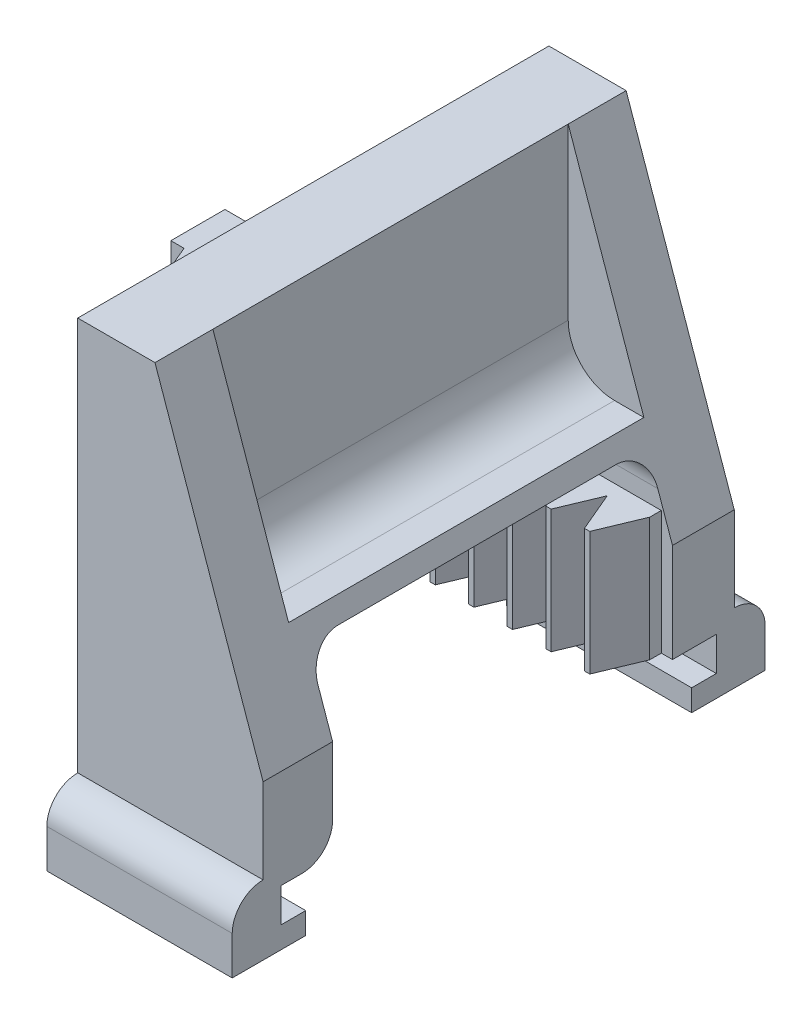
SolidWorks part; units mm, degrees
ref_plane "Front Plane" through (0, 0, 0) normal (0, 0, 1) x (1, 0, 0)
ref_plane "Top Plane" through (0, 0, 0) normal (0, 1, 0) x (1, 0, 0)
ref_plane "Right Plane" through (0, 0, 0) normal (1, 0, 0) x (0, 0, -1)
sketch "Sketch1" plane through (0, 0, 0) normal (0, 0, 1) x (1, 0, 0)
  line L0 (0, 0) -> (0, -30)
  line L1 (0, -30) -> (12, -30)
  line L2 (12, -30) -> (12, -20)
  line L3 (12, -20) -> (5, 0)
  line L4 (5, 0) -> (0, 0)
  dimension "D1" = 30
  dimension "D2" = 12
  dimension "D3" = 10
  dimension "D4" = 5
extrude "Boss-Extrude1" add sketch "Sketch1" against normal blind 30.5
sketch "Sketch4" plane through (0, 0, 0) normal (-1, 0, 0) x (0, 0, 1)
  line L0 (-30.5, 0) -> (-30.5, -30) construction
  line L1 (-26.5, -15.288) -> (-4.5, -15.288)
  line L2 (-26.5, -15.288) -> (-26.5, -30.288)
  line L3 (-26.5, -30.288) -> (-4.5, -30.288)
  line L4 (-4.5, -15.288) -> (-4.5, -30.288)
  point P4 (-26.5, -22.788)
  dimension "D1" = 22
  dimension "D2" = 15
  dimension "D3" = 4
extrude "Cut-Extrude2" cut sketch "Sketch4" against normal blind 25 contours L2 L1 L4 L3
ref_plane "Plane1" through (0, 0, -15.25) normal (0, 0, 1) x (1, 0, 0)
sketch "Sketch6" plane through (0, 0, -15.25) normal (0, 0, 1) x (1, 0, 0)
  line L0 (5, 0) -> (5, -14)
  line L1 (5, -14) -> (9.9, -14)
  line L2 (12, -20) -> (5, 0) construction
  line L3 (9.9, -14) -> (5, 0)
  dimension "D1" = 14
extrude "Cut-Extrude4" cut sketch "Sketch6" against normal mid plane 23
ref_plane "Plane2" through (0, -26.4, 0) normal (0, 1, 0) x (1, 0, 0)
sketch "Sketch7" plane through (0, -26.4, 0) normal (0, 1, 0) x (1, 0, 0)
  line L0 (11.2768, 29.25) -> (-19.7232, 29.25)
  line L62 (-16.5, 15.25) -> (16.5, 15.25) construction
  line L162 (11.2768, 29.25) -> (11.2768, 25.75)
  line L172 (-19.7232, 25.75) -> (-19.7232, 29.25)
  line L243 (11.2768, 25.75) -> (-19.7232, 25.75)
  dimension "D2" = 31
  dimension "D3" = 3.5
  dimension "D7" = 14
sketch "Sketch9" plane through (0, 0, 0) normal (-1, 0, 0) x (0, 0, 1)
  line L0 (-6.1597, -26.4) -> (-1.1597, -26.4)
  line L2 (-1.1597, -26.4) -> (-1.1597, -28.6)
  line L3 (-1.1597, -28.6) -> (-2.7597, -28.6)
  line L4 (-2.7597, -28.6) -> (-2.7597, -30.2967)
  line L5 (-2.7597, -30.2967) -> (-6.1597, -30.2967)
  line L6 (-6.1597, -30.2967) -> (-6.1597, -26.4)
  line L7 (-4.5, -30) -> (0, -30) construction
  line L15 (-15.25, -6.6) -> (-15.25, 6.6) construction
  line L16 (-27.7403, -30.2967) -> (-24.3403, -30.2967)
  line L17 (-27.7403, -28.6) -> (-27.7403, -30.2967)
  line L18 (-29.3403, -28.6) -> (-27.7403, -28.6)
  line L19 (-29.3403, -26.4) -> (-29.3403, -28.6)
  line L20 (-24.3403, -26.4) -> (-29.3403, -26.4)
  line L21 (-24.3403, -30.2967) -> (-24.3403, -26.4)
  dimension "D1" = 5
  dimension "D2" = 2.2
  dimension "D3" = 1.4
  dimension "D4" = 1.6
extrude "Boss-Extrude3" add sketch "Sketch7" along normal blind 8
sketch "Sketch10" plane through (0, -18.4, 0) normal (0, 1, 0) x (1, 0, 0)
  line L0 (11.2768, 25.75) -> (10.1347, 23.0104)
  line L2 (10.1347, 23.0104) -> (9.7913, 23.0104)
  line L3 (9.7913, 23.0104) -> (8.6309, 25.75)
  line L4 (-19.7232, 25.75) -> (11.2768, 25.75) construction
  line L5 (8.6309, 25.75) -> (11.2768, 25.75)
extrude "Boss-Extrude4" add sketch "Sketch10" against normal up to vertex (8 mm away) up to point (-19.7232, -26.4, -25.75)
pattern_linear "LPattern1" count 12 spacing 2.5 along (-1, 0, 0) of "Boss-Extrude4"
sketch "Sketch11" plane through (0, 0, -30.5) normal (0, 0, -1) x (-1, 0, 0)
  line L0 (-12, -30) -> (-12, -20) construction
  line L1 (-12, -25.5) -> (0, -25.5)
  line L2 (-12, -25.5) -> (-12, -30)
  line L3 (-12, -30) -> (0, -30)
  line L4 (0, -25.5) -> (0, -30)
  dimension "D1" = 4.5
extrude "Boss-Extrude5" add sketch "Sketch11" along normal blind 2
fillet "Fillet1" radius 2 1 edges at (6, -25.5, -32.5)
mirror "Mirror1" about plane through (0, 0, -15.25) normal (0, 0, 1) of "Boss-Extrude5"
fillet "Fillet2" radius 2 1 edges at (6, -25.5, 2)
extrude "Cut-Extrude5" cut sketch "Sketch9" against normal through all
fillet "Fillet4" radius 2 3 edges at (5.1754, -15.288, -4.5) (5.1754, -15.288, -26.5) (6, -26.4, -4.5)
fillet "Fillet5" radius 3 1 edges at (5, -14, -15.25)
